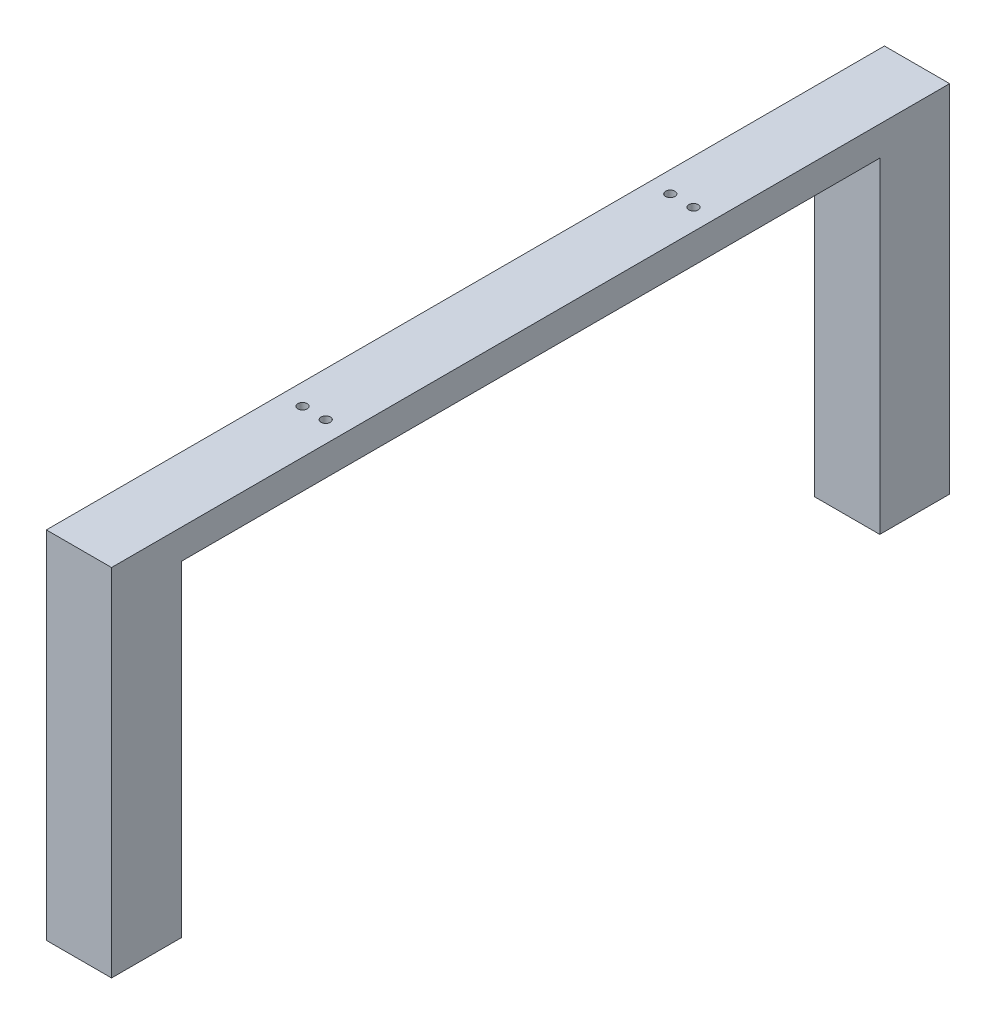
SolidWorks part; units mm, degrees
ref_plane "Front Plane" through (0, 0, 0) normal (0, 0, 1) x (1, 0, 0)
ref_plane "Top Plane" through (0, 0, 0) normal (0, 1, 0) x (1, 0, 0)
ref_plane "Right Plane" through (0, 0, 0) normal (1, 0, 0) x (0, 0, -1)
sketch "Sketch1" plane through (0, 0, 0) normal (1, 0, 0) x (0, 0, -1)
  line L0 (0, 0) -> (0, 19.2289) construction
  line L1 (-90, 0) -> (90, 0)
  line L2 (90, 0) -> (90, -76.35)
  line L3 (90, -76.35) -> (75, -76.35)
  line L4 (75, -76.35) -> (75, -6.35)
  line L5 (75, -6.35) -> (-75, -6.35)
  line L7 (-75, -76.35) -> (-75, -6.35)
  line L8 (-90, -76.35) -> (-75, -76.35)
  line L9 (-90, 0) -> (-90, -76.35)
  point P5 (0, 0)
  point P9 (0, 0)
  point P12 (0, -6.35)
  dimension "D1" = 6.35
  dimension "D2" = 75
  dimension "D3" = 15
  dimension "D4" = 70
extrude "Boss-Extrude1" add sketch "Sketch1" along normal blind 7 and the other way blind 7
sketch "Sketch2" plane through (0, 0, 0) normal (0, 1, 0) x (1, 0, 0)
  line L0 (0, 0) -> (7, 0) construction
  line L1 (7, 90) -> (7, -90) construction
  line L2 (0, 0) -> (0, 60.3243) construction
  circle A0 centre (2.5, 39.5) radius 1
  circle A1 centre (-2.5, 39.5) radius 1
  circle A2 centre (2.5, -39.5) radius 1
  circle A3 centre (-2.5, -39.5) radius 1
  point P10 (3.265, 38.1825)
  dimension "D2" = 2.5
  dimension "D3" = 2
  dimension "D1" = 39.5
extrude "Cut-Extrude1" cut sketch "Sketch2" against normal through all
